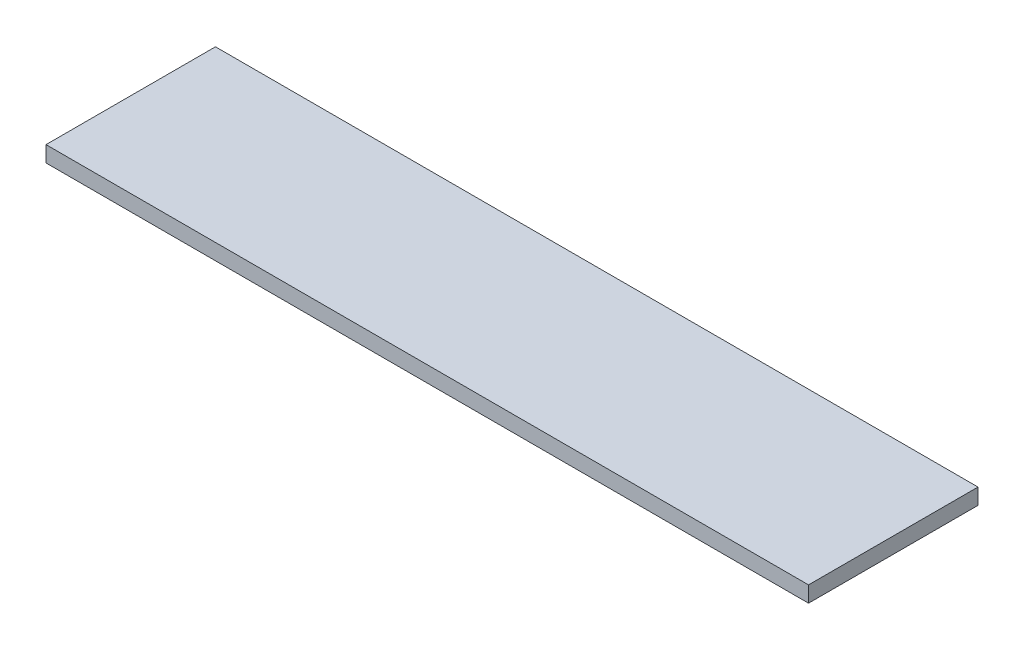
SolidWorks part; units mm, degrees
ref_plane "Front Plane" through (0, 0, 0) normal (0, 0, 1) x (1, 0, 0)
ref_plane "Top Plane" through (0, 0, 0) normal (0, 1, 0) x (1, 0, 0)
ref_plane "Right Plane" through (0, 0, 0) normal (1, 0, 0) x (0, 0, -1)
sketch "Sketch1" plane through (0, 0, 0) normal (0, 1, 0) x (1, 0, 0)
  line L1 (0, 0) -> (457.2, 0)
  line L2 (0, 0) -> (0, 101.6)
  line L3 (0, 101.6) -> (457.2, 101.6)
  line L4 (457.2, 0) -> (457.2, 101.6)
  dimension "D1" = 457.2
  dimension "D2" = 101.6
extrude "Boss-Extrude1" add sketch "Sketch1" along normal blind 9.525
